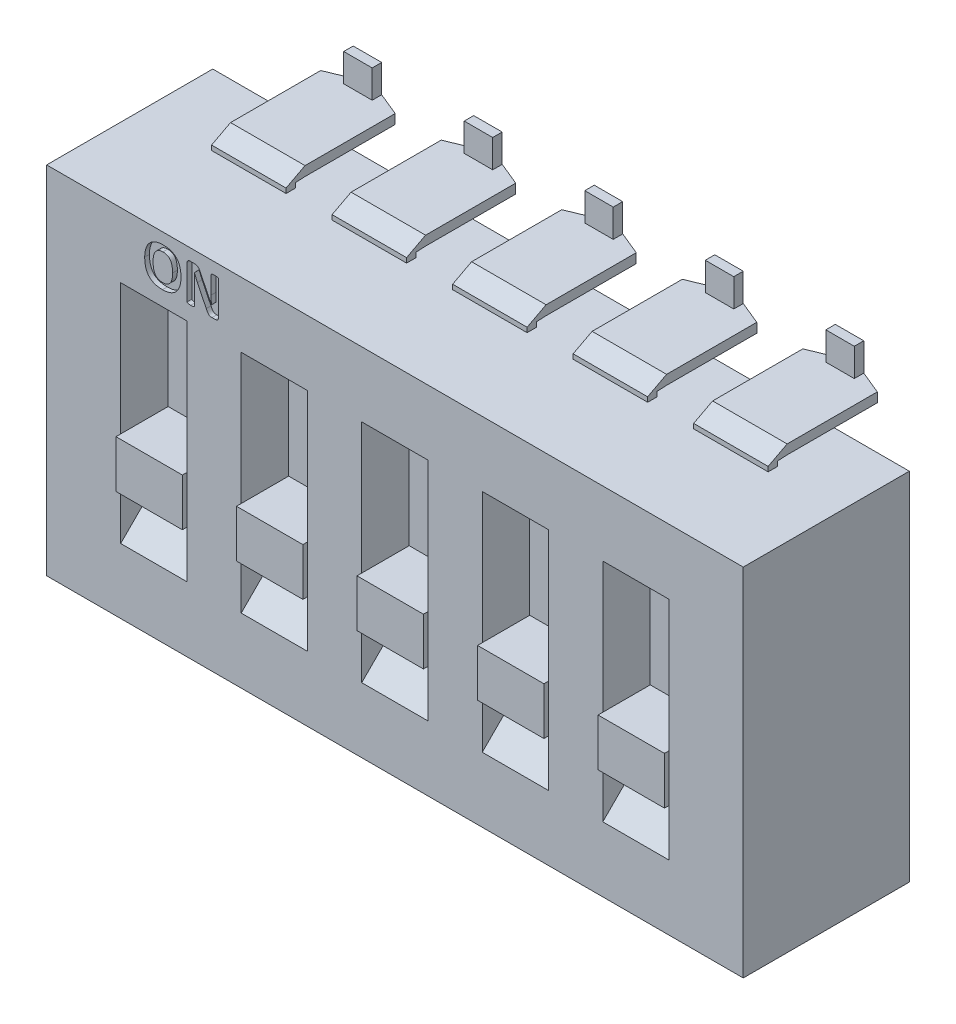
SolidWorks part; units mm, degrees
other "Детальный элемент1"
ref_plane "Спереди" through (0, 0, 0) normal (0, 0, 1) x (1, 0, 0)
ref_plane "Сверху" through (0, 0, 0) normal (0, 1, 0) x (1, 0, 0)
ref_plane "Справа" through (0, 0, 0) normal (1, 0, 0) x (0, 0, -1)
ref_plane "Плоскость1" through (0, 0, 1) normal (0, 0, 1) x (1, 0, 0)
sketch "Эскиз1" plane through (0, 0, 1) normal (0, 0, 1) x (1, 0, 0)
  line L1 (-7.34, -3.75) -> (7.34, -3.75)
  line L2 (-7.34, -3.75) -> (-7.34, 3.75)
  line L3 (-7.34, 3.75) -> (7.34, 3.75)
  line L4 (7.34, -3.75) -> (7.34, 3.75)
  line L5 (-7.34, -3.75) -> (7.34, 3.75) construction
  line L6 (-7.34, 3.75) -> (7.34, -3.75) construction
  point P0 (0, 0)
  dimension "D1" = 7.5
  dimension "D2" = 14.68
extrude "Бобышка-Вытянуть1" add sketch "Эскиз1" along normal blind 3.5
sketch "Эскиз2" plane through (0, -3.75, 0) normal (0, -1, 0) x (1, 0, 0)
  line L0 (-7.34, 1) -> (7.34, 1) construction
  line L1 (-5.865, 2.5) -> (-4.295, 2.5)
  line L2 (-5.865, 2.5) -> (-5.865, 2.3)
  line L3 (-5.865, 2.3) -> (-4.295, 2.3)
  line L4 (-4.295, 2.5) -> (-4.295, 2.3)
  line L5 (-5.865, 2.5) -> (-4.295, 2.3) construction
  line L6 (-5.865, 2.3) -> (-4.295, 2.5) construction
  line L7 (-7.34, 4.5) -> (-7.34, 1) construction
  point P0 (-5.08, 2.4)
  dimension "D1" = 1.57
  dimension "D2" = 0.2
  dimension "D3" = 1.4
  dimension "D4" = 2.26
extrude "Бобышка-Вытянуть2" add sketch "Эскиз2" along normal blind 0.1 separate body
sketch "Эскиз3" plane through (0, 0, 0) normal (0, 0, 1) x (1, 0, 0)
  line L1 (-5.38, -3.86) -> (-4.78, -3.86)
  line L2 (-5.38, -3.86) -> (-5.38, -4.65)
  line L3 (-5.38, -4.65) -> (-4.78, -4.65)
  line L4 (-4.78, -3.86) -> (-4.78, -4.65)
  line L5 (-5.38, -3.86) -> (-4.78, -4.65) construction
  line L6 (-5.38, -4.65) -> (-4.78, -3.86) construction
  point P0 (-5.08, -4.255)
  dimension "D1" = 0.6
  dimension "D2" = 0.79
  dimension "D3" = 4.65
extrude "Бобышка-Вытянуть3" add sketch "Эскиз3" along normal blind 0.2 separate body
sketch "Эскиз4" plane through (0, 0, 0.2) normal (0, 0, 1) x (1, 0, 0)
  line L0 (-4.78, -3.86) -> (-5.38, -3.86) construction
  line L1 (-5.865, -3.86) -> (-4.295, -3.86)
  line L2 (-5.865, -3.86) -> (-5.865, -4.06)
  line L3 (-5.865, -4.06) -> (-4.295, -4.06)
  line L4 (-4.295, -3.86) -> (-4.295, -4.06)
  dimension "D1" = 0.2
extrude "Бобышка-Вытянуть4" add sketch "Эскиз4" along normal offset from surface (1.9 mm away) 0.2 up to face at (-5.08, -3.8, 2.3)
chamfer "Фаска1" distance 0.2 distance2 0.485 2 edges at (-4.78, -3.96, 0.2) (-5.38, -3.96, 0.2) first distance on face at (-4.78, -4.216, 0.12) first distance on face at (-5.38, -4.216, 0.12)
loft "По сечениям1" add section face at (-5.08, -3.85, 2.4) section face at (-5.08, -3.96, 2.1) connector at (-4.295, -3.85, 2.5) connector at (-4.295, -4.06, 2.1)
sketch "Эскиз5" plane through (0, 0, 4.5) normal (0, 0, 1) x (1, 0, 0)
  line L5 (-5.78, 1.38) -> (-4.38, 1.38)
  line L6 (-5.78, 1.38) -> (-5.78, -1.38)
  line L7 (-5.78, -1.38) -> (-4.38, -1.38)
  line L8 (-4.38, 1.38) -> (-4.38, -1.38)
  line L9 (-5.78, 1.38) -> (-4.38, -1.38) construction
  line L10 (-5.78, -1.38) -> (-4.38, 1.38) construction
  point P0 (-5.08, 0)
  dimension "D1" = 2.76
  dimension "D2" = 1.4
extrude "Вырез-Вытянуть1" cut sketch "Эскиз5" against normal blind 1
chamfer "Фаска2" distance 1 angle 45 2 edges at (-5.08, 1.38, 4.5) (-5.08, -1.38, 4.5)
sketch "Эскиз6" plane through (0, 0, 3.5) normal (0, 0, 1) x (1, 0, 0)
  line L0 (-4.38, -1.38) -> (-4.38, 1.38) construction
  line L1 (-5.78, -1.38) -> (-4.38, -1.38)
  line L2 (-5.78, -1.38) -> (-5.78, -0.38)
  line L3 (-5.78, -0.38) -> (-4.38, -0.38)
  line L4 (-4.38, -1.38) -> (-4.38, -0.38)
  dimension "D1" = 1
extrude "Бобышка-Вытянуть5" add sketch "Эскиз6" along normal blind 1.1 separate body
mirror "Зеркальное отражение1" about plane through (0, 0, 0) normal (0, 1, 0) of bodies 111
pattern_linear "Линейный массив3" count 5 spacing 2.54 along (1, 0, 0) of "Вырез-Вытянуть1", "Фаска2"
pattern_linear "Линейный массив1" count 5 spacing 2.54 along (1, 0, 0) of bodies 120 111 113
sketch "Эскиз7" plane through (0, 0, 4.5) normal (0, 0, 1) x (1, 0, 0)
  text T0 "ON" font "Calibri" height 0.8
extrude "Вырез-Вытянуть2" cut sketch "Эскиз7" against normal blind 0.1
equation "\"N\"= 5"
equation "\"D2@Эскиз1\"=\"N\"*2.54+1.98"
equation "\"D1@Линейный массив1\"=\"N\""
equation "\"D1@Линейный массив2\"=\"N\""
equation "\"D1@Линейный массив3\"=\"N\""
